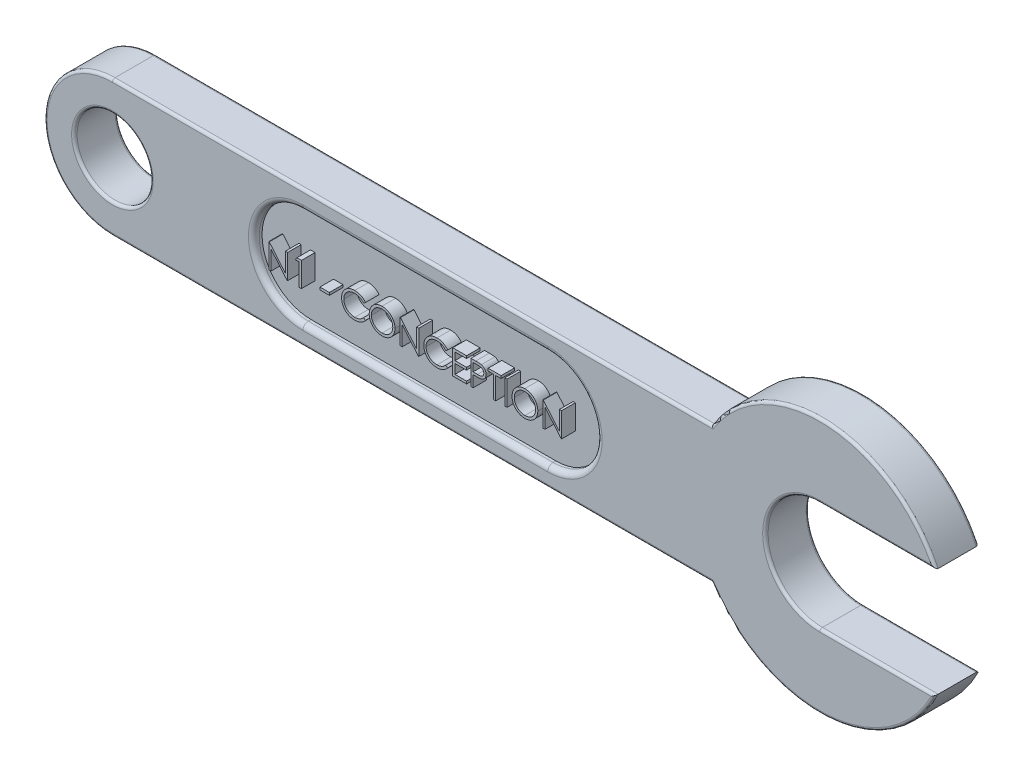
SolidWorks part; units mm, degrees
ref_plane "Front Plane" through (0, 0, 0) normal (0, 0, 1) x (1, 0, 0)
ref_plane "Top Plane" through (0, 0, 0) normal (0, 1, 0) x (1, 0, 0)
ref_plane "Right Plane" through (0, 0, 0) normal (1, 0, 0) x (0, 0, -1)
sketch "Sketch2" plane through (0, 0, 0) normal (0, 0, 1) x (1, 0, 0)
  line L0 (0, 0) -> (0, 46344.8058) construction
  line L1 (0, 0) -> (46344.8058, 0) construction
  line L2 (-22.5, 0) -> (22.5, 0) construction
  line L3 (-22.5, 6) -> (22.5, 6)
  line L4 (-22.5, -6) -> (22.5, -6)
  line L5 (-22.5, 0) -> (22.5, 0) construction
  line L6 (-22.5, 9) -> (22.5, 9)
  line L7 (-22.5, -9) -> (22.5, -9)
  line L8 (-57.5, 0) -> (22.5, 0) construction
  line L9 (-57.5, 12.5) -> (22.5, 12.5)
  line L10 (-57.5, -12.5) -> (22.5, -12.5)
  line L11 (72.5, 10) -> (93.7662, 10)
  line L12 (72.5, -10) -> (93.7662, -10)
  line L13 (22.5, 12.5) -> (52.6003, 12.5)
  line L14 (22.5, -12.5) -> (52.6003, -12.5)
  arc A0 (-22.5, 6) -> (-22.5, -6) centre (-22.5, 0) ccw
  arc A1 (22.5, -6) -> (22.5, 6) centre (22.5, 0) ccw
  arc A2 (-22.5, 9) -> (-22.5, -9) centre (-22.5, 0) ccw
  arc A3 (22.5, -9) -> (22.5, 9) centre (22.5, 0) ccw
  arc A4 (-57.5, 12.5) -> (-57.5, -12.5) centre (-57.5, 0) ccw
  circle A6 centre (-57.5, 0) radius 6
  arc A7 (93.7662, 10) -> (52.6003, 12.5) centre (72.5, 0) ccw
  arc A8 (72.5, 10) -> (72.5, -10) centre (72.5, 0) ccw
  circle A9 centre (-57.5, 0) radius 7
  arc A10 (52.6003, -12.5) -> (93.7662, -10) centre (72.5, 0) ccw
  point P7 (0, 0)
  point P12 (0, 0)
  point P29 (0, 0)
  dimension "D2" = 47
  dimension "D3" = 20
  dimension "D5" = 9
  dimension "D6" = 6
  dimension "D7" = 12
  dimension "D8" = 12.5
  dimension "D9" = 14
  dimension "D1" = 130
  dimension "D4" = 45
  dimension "D10" = 35
extrude "Boss-Extrude1" add sketch "Sketch2" along normal mid plane 8 contours L14 A10 L12 A8 L11 A7 L13 L9 A4 L10 A3 L7 A2 L6 A9 region at (-17.5, 10.7962, 0)
extrude "Boss-Extrude3" add sketch "Sketch2<4>" along normal mid plane 5 contours L4 A1 L3 A0 | L7 A3 L6 A2 A1 L4 A0 L3 region at (0, 0, 0) region at (0, 8.3448, 0)
sketch "Sketch2<4>" plane through (0, 0, 0) normal (0, 0, 1) x (1, 0, 0) same geometry as "Sketch2"
fillet "Fillet1" radius 0.5 14 edges at (83.1331, 10, -4) (83.1331, -10, -4) (83.1331, 10, 4) (83.1331, -10, 4) (-2.4499, -12.5, 4) (-70, 0, 4) (-50.5, 0, 4) (-50.5, 0, -4) (62.5, 0, -4) (73.9245, 23.4568, -4) (73.9245, -23.4568, 4) (62.5, 0, 4) (73.9245, 23.4568, 4) (-2.4499, 12.5, 4)
fillet "Fillet2" radius 1 8 edges at (-31.5, 0, 4) (0, -9, 4) (31.5, 0, 4) (-31.5, 0, -4) (0, -9, -4) (31.5, 0, -4) (0, 9, 4) (0, 9, -4)
fillet "Fillet3" radius 0.5 3 edges at (-2.1534, 12.5, -4) (-2.4499, -12.5, -4) (-70, 0, -4)
sketch "Sketch3" plane through (0, 0, 2.5) normal (0, 0, 1) x (1, 0, 0)
  text T0 "N1 - CONCEPTION" font "Century Gothic" height 4.5
extrude "Boss-Extrude4" add sketch "Sketch3" along normal mid plane 5
